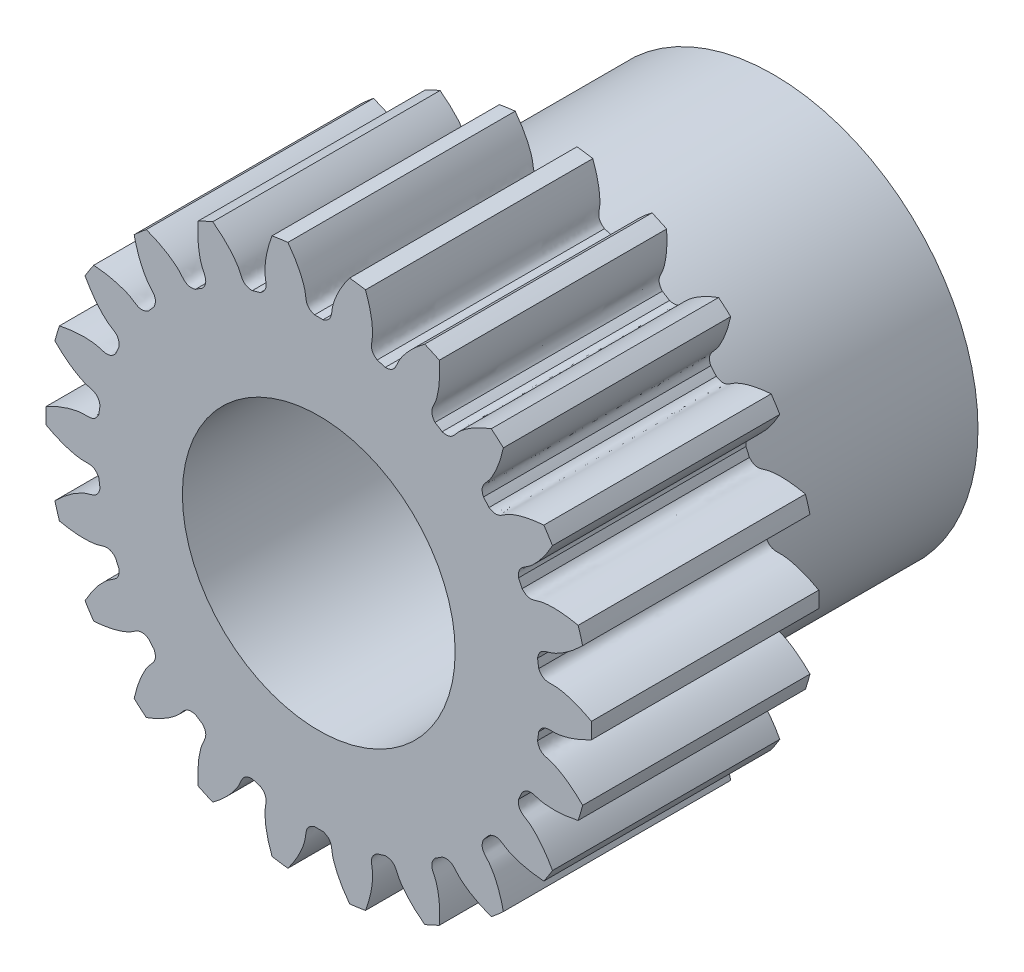
SolidWorks part; units mm, degrees
ref_plane "前视基准面" through (0, 0, 0) normal (0, 0, 1) x (1, 0, 0)
ref_plane "上视基准面" through (0, 0, 0) normal (0, 1, 0) x (1, 0, 0)
ref_plane "右视基准面" through (0, 0, 0) normal (1, 0, 0) x (0, 0, -1)
sketch "草图1" plane through (0, 0, 0) normal (0, 0, 1) x (1, 0, 0)
  circle A0 centre (0, 0) radius 12
extrude "凸台-拉伸1" add sketch "草图1" along normal blind 10
ref_axis "基准轴1" through (0, 0, -0.5) along (0, 0, 1)
sketch "草图2" plane through (0, 0, 0) normal (0, 0, 1) x (1, 0, 0)
  line L0 (0, 0) -> (0, 12) construction
  circle A0 centre (0, 0) radius 12 construction
  arc A1 (0.1857, 9.7482) -> (-0.1857, 9.7482) centre (0, 0) ccw
  arc A2 (3.0856, 13.5599) -> (-3.0856, 13.5599) centre (0, 0) ccw
  spline S0 degree 3 poles (0.1857, 9.7482) (0.5882, 9.8762) (0.5483, 10.1518) (0.5996, 10.4216) (0.606, 10.4519) (0.6139, 10.4862) (0.6235, 10.5243) (0.6349, 10.5661) (0.6484, 10.6117) (0.664, 10.661) (0.6819, 10.7139) (0.7023, 10.7703) (0.7253, 10.8301) (0.7511, 10.8933) (0.7797, 10.9597) (0.8114, 11.0293) (0.8462, 11.1021) (0.8843, 11.1778) (0.9259, 11.2563) (0.9711, 11.3377) (1.0199, 11.4217) (1.0726, 11.5082) (1.1292, 11.5972) (1.1899, 11.6884) (1.2547, 11.7818) (1.3238, 11.8773) (1.3973, 11.9746) (1.4753, 12.0737) (1.5579, 12.1744) (1.6452, 12.2766) (1.7372, 12.3802) (1.8341, 12.4849) (1.9359, 12.5906) (2.0428, 12.6972) (2.1547, 12.8044) (2.2718, 12.9123) (2.3942, 13.0205) (2.5218, 13.1289) (2.6548, 13.2373) (2.8415, 13.3834) (2.9864, 13.49) (3.0856, 13.5599) knots 0 0 0 0 0.157021 0.162531 0.168888 0.176093 0.184146 0.193046 0.202794 0.213389 0.224833 0.237123 0.250262 0.264248 0.279082 0.294763 0.311292 0.328669 0.346893 0.365965 0.385884 0.406652 0.428266 0.450729 0.474039 0.498197 0.523202 0.549055 0.575756 0.603304 0.6317 0.660944 0.691035 0.721974 0.75376 0.786395 0.819876 0.854206 0.889383 0.925408 1 1 1 1
  spline S1 degree 3 poles (-0.1857, 9.7482) (-0.5882, 9.8762) (-0.5483, 10.1518) (-0.5996, 10.4216) (-0.606, 10.4519) (-0.6139, 10.4862) (-0.6235, 10.5243) (-0.6349, 10.5661) (-0.6484, 10.6117) (-0.664, 10.661) (-0.6819, 10.7139) (-0.7023, 10.7703) (-0.7253, 10.8301) (-0.7511, 10.8933) (-0.7797, 10.9597) (-0.8114, 11.0293) (-0.8462, 11.1021) (-0.8843, 11.1778) (-0.9259, 11.2563) (-0.9711, 11.3377) (-1.0199, 11.4217) (-1.0726, 11.5082) (-1.1292, 11.5972) (-1.1899, 11.6884) (-1.2547, 11.7818) (-1.3238, 11.8773) (-1.3973, 11.9746) (-1.4753, 12.0737) (-1.5579, 12.1744) (-1.6452, 12.2766) (-1.7372, 12.3802) (-1.8341, 12.4849) (-1.9359, 12.5906) (-2.0428, 12.6972) (-2.1547, 12.8044) (-2.2718, 12.9123) (-2.3942, 13.0205) (-2.5218, 13.1289) (-2.6548, 13.2373) (-2.8415, 13.3834) (-2.9864, 13.49) (-3.0856, 13.5599) knots 0 0 0 0 0.157021 0.162531 0.168888 0.176093 0.184146 0.193046 0.202794 0.213389 0.224833 0.237123 0.250262 0.264248 0.279082 0.294763 0.311292 0.328669 0.346893 0.365965 0.385884 0.406652 0.428266 0.450729 0.474039 0.498197 0.523202 0.549055 0.575756 0.603304 0.6317 0.660944 0.691035 0.721974 0.75376 0.786395 0.819876 0.854206 0.889383 0.925408 1 1 1 1
extrude "切除-拉伸1" cut sketch "草图2" along normal through all
pattern_circular "阵列(圆周)1" count 22 every 16.364 about axis through (0, 0, -0.5) along (0, 0, 1) of "切除-拉伸1"
sketch "草图3" plane through (0, 0, 0) normal (0, 0, 1) x (1, 0, 0)
  circle A0 centre (0, 0) radius 11 construction
  dimension "Dn" = 22
sketch "草图4" plane through (0, 0, 0) normal (0, 0, 1) x (1, 0, 0)
  circle A0 centre (0, 0) radius 9
  dimension "D1" = 18
extrude "凸台-拉伸2" add sketch "草图4" against normal blind 10
sketch "草图5" plane through (0, 0, -10) normal (0, 0, -1) x (-1, 0, 0)
  circle A0 centre (0, 0) radius 6
  dimension "D1" = 12
extrude "切除-拉伸2" cut sketch "草图5" against normal through all
